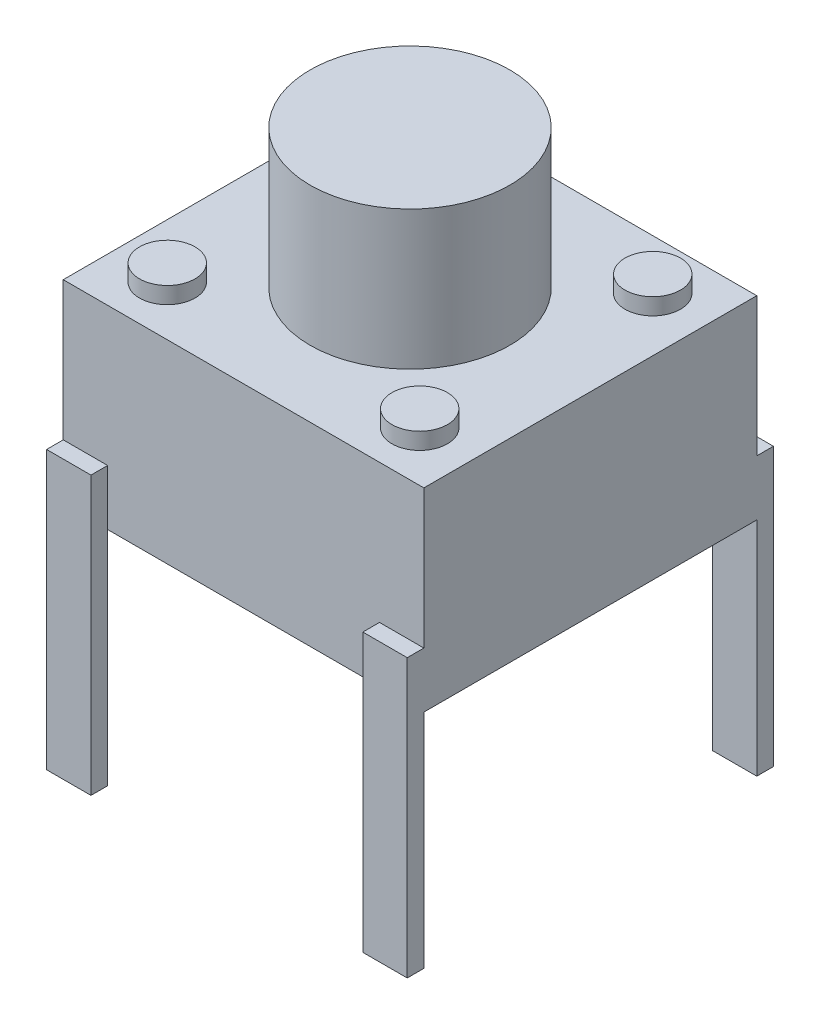
SolidWorks part; units mm, degrees
ref_plane "前视基准面" through (0, 0, 0) normal (0, 0, 1) x (1, 0, 0)
ref_plane "上视基准面" through (0, 0, 0) normal (0, 1, 0) x (1, 0, 0)
ref_plane "右视基准面" through (0, 0, 0) normal (1, 0, 0) x (0, 0, -1)
other "Configuration Table"
sketch "草图1" plane through (0, 0, 0) normal (0, 1, 0) x (1, 0, 0)
  line L1 (-3.25, -3) -> (3.25, -3)
  line L2 (-3.25, -3) -> (-3.25, 3)
  line L3 (-3.25, 3) -> (3.25, 3)
  line L4 (3.25, -3) -> (3.25, 3)
  line L5 (-3.25, -3) -> (3.25, 3) construction
  line L6 (-3.25, 3) -> (3.25, -3) construction
  circle A0 centre (0, 0) radius 1.8
  circle A1 centre (-2.275, 2.1) radius 0.5
  circle A2 centre (-2.275, -2.1) radius 0.5
  circle A3 centre (2.275, -2.1) radius 0.5
  circle A4 centre (2.275, 2.1) radius 0.5
  point P0 (0, 0)
  dimension "D3" = 3.6
  dimension "D5" = 1
  dimension "D1" = 6
  dimension "D2" = 6.5
  dimension "D4" = 4.2
extrude "凸台-拉伸1" add sketch "草图1" along normal blind 3.5 contours L3 L4 L1 L2
extrude "凸台-拉伸2" add sketch "草图1<3>" along normal blind 6 contours A0
sketch "草图1<3>" plane through (0, 0, 0) normal (0, 1, 0) x (1, 0, 0) same geometry as "草图1"
extrude "凸台-拉伸3" add sketch "草图1<4>" along normal blind 0.3 from surface contours A1 | A2 | A4 | A3 starting at face at (0, 3.5, -1.8)
sketch "草图1<4>" plane through (0, 0, 0) normal (0, 1, 0) x (1, 0, 0) same geometry as "草图1"
sketch "草图2" plane through (0, 0, 0) normal (0, -1, 0) x (1, 0, 0)
  line L1 (-3.25, 3) -> (-2.45, 3)
  line L2 (-3.25, 3) -> (-3.25, 3.3)
  line L3 (-3.25, 3.3) -> (-2.45, 3.3)
  line L4 (-2.45, 3) -> (-2.45, 3.3)
  line L5 (-3.25, -3) -> (3.25, -3) construction
  line L6 (3.25, 3) -> (2.45, 3)
  line L7 (3.25, 3) -> (3.25, 3.3)
  line L8 (3.25, 3.3) -> (2.45, 3.3)
  line L9 (2.45, 3) -> (2.45, 3.3)
  line L10 (-3.25, -3) -> (-2.45, -3)
  line L11 (-3.25, -3) -> (-3.25, -3.3)
  line L12 (-3.25, -3.3) -> (-2.45, -3.3)
  line L13 (-2.45, -3) -> (-2.45, -3.3)
  line L15 (2.45, -3) -> (3.25, -3)
  line L16 (2.45, -3) -> (2.45, -3.3)
  line L17 (2.45, -3.3) -> (3.25, -3.3)
  line L18 (3.25, -3) -> (3.25, -3.3)
  dimension "D1" = 0.3
  dimension "D2" = 0.8
extrude "凸台-拉伸4" add sketch "草图2" along normal blind 5 from offset 1 offset against normal yes
